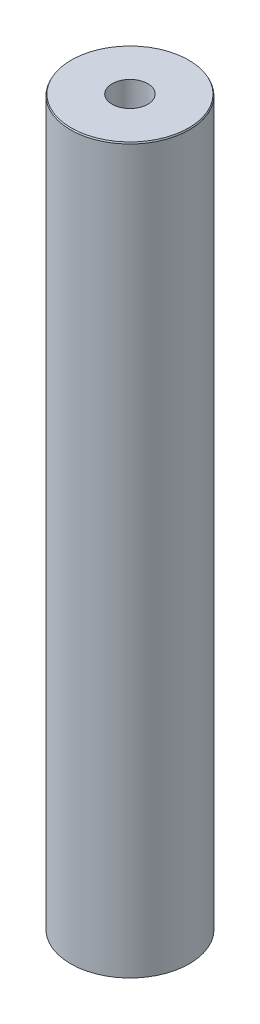
SolidWorks part; units mm, degrees
ref_plane "Front Plane" through (0, 0, 0) normal (0, 0, 1) x (1, 0, 0)
ref_plane "Top Plane" through (0, 0, 0) normal (0, 1, 0) x (1, 0, 0)
ref_plane "Right Plane" through (0, 0, 0) normal (1, 0, 0) x (0, 0, -1)
sketch "Sketch1" plane through (0, 0, 0) normal (0, 1, 0) x (1, 0, 0)
  circle A0 centre (0, 0) radius 47.5
  dimension "SHAFT_OD" = 95
extrude "Boss-Extrude1" add sketch "Sketch1" along normal blind 578.926
sketch "Sketch2" plane through (0, 0, 0) normal (0, 1, 0) x (1, 0, 0)
  circle A0 centre (0, 0) radius 14.2789
  dimension "BORE_D" = 28.5579
extrude "Cut-Extrude1" cut sketch "Sketch2" along normal through all
chamfer "Chamfer1" distance 1.0836 angle 25.739 2 edges at (0, 578.926, 47.5) (0, 0, 47.5) first distance on face at (0, 578.926, 47.5) first distance on face at (0, 0, 14.2789)
